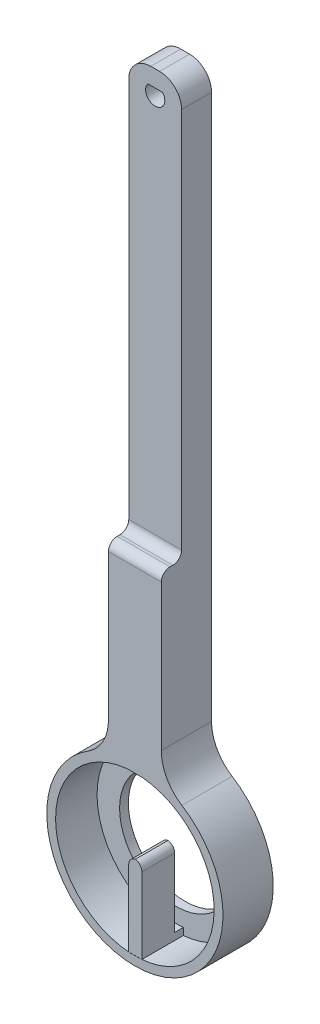
SolidWorks part; units mm, degrees
ref_plane "Front Plane" through (0, 0, 0) normal (0, 0, 1) x (1, 0, 0)
ref_plane "Top Plane" through (0, 0, 0) normal (0, 1, 0) x (1, 0, 0)
ref_plane "Right Plane" through (0, 0, 0) normal (1, 0, 0) x (0, 0, -1)
sketch "Sketch1" plane through (0, 0, 0) normal (0, 0, 1) x (1, 0, 0)
  line L1 (-4, -87.5) -> (4, -87.5)
  line L2 (-4, -87.5) -> (-4, 87.5)
  line L3 (-4, 87.5) -> (4, 87.5)
  line L4 (4, -87.5) -> (4, 87.5)
  line L5 (-4, -87.5) -> (4, 87.5) construction
  line L6 (-4, 87.5) -> (4, -87.5) construction
  circle A0 centre (0, 87.5) radius 4
  circle A1 centre (0, -87.5) radius 20
  point P0 (0, 0)
  dimension "D1" = 8
  dimension "D2" = 175
extrude "Boss-Extrude1" add sketch "Sketch1" along normal blind 13 contours A1 L4 A0 L2 | L2 A1 L4 L1 | L3 A0 | L3 A0 region at (0, -88.9381, 0) region at (0, 8.3647, 0) region at (0, 89.1977, 0) region at (0, 85.8023, 0)
extrude "Boss-Extrude2" add sketch "Sketch1<3>" along normal blind 13 contours L4 A1 L2 L1 region at (0, -77.5667, 0)
sketch "Sketch1<3>" plane through (0, 0, 0) normal (0, 0, 1) x (1, 0, 0) same geometry as "Sketch1"
sketch "Sketch2" plane through (0, 0, 13) normal (0, 0, 1) x (1, 0, 0)
  line L0 (-4, 87.5) -> (4, 87.5) construction
  line L1 (0, 84.375) -> (0, 89.875) construction
  line L2 (-1.8367, 90.0283) -> (1.8367, 90.0283)
  circle A0 centre (0, 87.5) radius 3.125
  circle A1 centre (0, 62.5) radius 3.125
  point P12 (0, 89.875)
  point P13 (0, 90.0283)
  dimension "D1" = 5.5
  dimension "D2" = 2
extrude "Cut-Extrude1" cut sketch "Sketch2" against normal blind 13 contours A0 region at (0, 87.3585, 13)
sketch "Sketch3" plane through (4, 0, 0) normal (1, 0, 0) x (0, 0, -1)
  line L1 (-13, 91.5) -> (-6.3732, 91.5)
  line L2 (-13, 91.5) -> (-13, 72.0797)
  line L3 (-13, 72.0797) -> (-6.3732, 72.0797)
  line L4 (-6.3732, 91.5) -> (-6.3732, 72.0797)
extrude "Cut-Extrude2" cut sketch "Sketch3" against normal blind 13
fillet "Fillet1" radius 10 1 edges at (0, 72.0797, 6.3732)
sketch "Sketch4" plane through (0, 0, 13) normal (0, 0, 1) x (1, 0, 0)
  line L0 (-20, -87.5) -> (20, -87.5) construction
  line L1 (0, -107.5) -> (0, -69.6414) construction
  arc A0 (-4, -67.9041) -> (4, -67.9041) centre (0, -87.5) ccw construction
  circle A1 centre (0, -87.5) radius 20
extrude "Boss-Extrude3" add sketch "Sketch4" along normal blind 13
sketch "Sketch5" plane through (4, 0, 0) normal (1, 0, 0) x (0, 0, -1)
  line L0 (-13, -67.9041) -> (-13, 72.0797) construction
  line L1 (-13, 61.0572) -> (-13, 87.5)
  line L2 (-13, 87.5) -> (-6.3732, 87.5)
  arc A0 (-6.3732, 87.5) -> (-13, 61.0572) centre (-49.1244, 84.1621) cw
extrude "Cut-Extrude3" cut sketch "Sketch5" against normal blind 13
sketch "Sketch6" plane through (0, 0, 26) normal (0, 0, 1) x (1, 0, 0)
  circle A0 centre (0, -87.5) radius 18
extrude "Cut-Extrude4" cut sketch "Sketch6" against normal blind 24
sketch "Sketch8" plane through (0, 0, 2) normal (0, 0, 1) x (1, 0, 0)
  line L0 (-1.3907, -105.4462) -> (-1.3907, -86.4462)
  line L1 (1.6093, -86.4462) -> (1.6093, -105.4279)
  line L2 (-1.3907, -86.4462) -> (1.6093, -86.4462)
  line L3 (-1.3907, -105.4462) -> (1.6093, -105.4279)
  line L4 (17.1093, -101.2315) -> (17.1093, -73.7685)
  line L5 (-16.8907, -100.8575) -> (-16.8907, -74.1425)
  circle A0 centre (0, -87.5) radius 18 construction
  point P9 (17.1093, -87.5)
  point P12 (-16.8907, -87.5)
  dimension "D1" = 3
  dimension "D2" = 19
  dimension "D3" = 15.5
  dimension "D4" = 15.5
extrude "Boss-Extrude7" add sketch "Sketch8" along normal blind 22 separate body contours L3 L1 L2 L0
fillet "Fillet5" radius 1.75 2 edges at (1.6093, -86.4462, 13) (-1.3907, -86.4462, 13)
fillet "Fillet6" radius 20 1 edges at (0, 61.0572, 13)
sketch "Sketch13" plane through (-4, 0, 0) normal (-1, 0, 0) x (0, 0, 1)
  line L0 (6.3732, 87.5) -> (6.3732, 3.1735)
  line L1 (6.3732, 3.1735) -> (13, 3.1735)
  line L2 (13, -67.9041) -> (13, 55.8052) construction
  line L3 (13, 3.1735) -> (13, 87.5)
  line L4 (13, 87.5) -> (6.3732, 87.5)
extrude "Cut-Extrude8" cut sketch "Sketch13" against normal blind 22
fillet "Fillet8" radius 21.5 1 edges at (0, 3.1735, 6.3732)
fillet "Fillet9" radius 21.5 1 edges at (0, 3.1735, 13)
sketch "Sketch14" plane through (-4, 0, 0) normal (-1, 0, 0) x (0, 0, 1)
  line L1 (6.3732, -28.0179) -> (23.434, -28.0179)
  line L2 (6.3732, -28.0179) -> (6.3732, 18.6989)
  line L3 (6.3732, 18.6989) -> (23.434, 18.6989)
  line L4 (23.434, -28.0179) -> (23.434, 18.6989)
extrude "Cut-Extrude10" cut sketch "Sketch14" against normal blind 22
sketch "Sketch23" plane through (0, 0, 0) normal (0, 0, -1) x (-1, 0, 0)
  circle A0 centre (0, -87.5) radius 16.3958
extrude "Cut-Extrude14" cut sketch "Sketch23" against normal blind 4
sketch "Sketch24" plane through (0, 0, 0) normal (0, 0, -1) x (-1, 0, 0)
  arc A0 (0, -71.1042) -> (0, -103.8958) centre (0, -87.5) ccw
  circle A1 centre (0, -87.5) radius 16.3958 construction
  arc A2 (0, -71.1042) -> (0, -103.8958) centre (0, -87.5) cw
  arc A3 (0, -74.7441) -> (0, -100.5129) centre (0, -87.6285) cw
  arc A4 (0, -74.7441) -> (0, -100.5129) centre (0, -87.6285) ccw
extrude "Boss-Extrude16" add sketch "Sketch24" against normal blind 2
sketch "Sketch25" plane through (0, 0, 26) normal (0, 0, 1) x (1, 0, 0)
  circle A0 centre (0, -87.6285) radius 20.1285
extrude "Cut-Extrude15" cut sketch "Sketch25" against normal blind 9
sketch "Sketch26" plane through (0, 0, 6.3732) normal (0, 0, 1) x (1, 0, 0)
  line L0 (-4, 80.8242) -> (-4, -28.0179) construction
  line L1 (-4, 66.3734) -> (4.8485, 66.3734)
  line L2 (-4, 66.3734) -> (-4, 92.3734)
  line L3 (-4, 92.3734) -> (4.8485, 92.3734)
  line L4 (4.8485, 66.3734) -> (4.8485, 92.3734)
  dimension "D1" = 26
extrude "Cut-Extrude16" cut sketch "Sketch26" against normal blind 9 contours L2 L1 L4 L3
sketch "Sketch27" plane through (0, 0, 6.3732) normal (0, 0, 1) x (1, 0, 0)
  line L0 (0, 58.1905) -> (0, 63.6905) construction
  line L1 (-2.1323, 63.8405) -> (2.1323, 63.8405)
  circle A0 centre (0, 61.4179) radius 3.2274
  dimension "D1" = 5.5
  dimension "D2" = 0.15
extrude "Cut-Extrude17" cut sketch "Sketch27" against normal blind 9 contours L1 A0 region at (0, 61.2051, 6.3732)
fillet "Fillet21" radius 3.5 2 edges at (4, 66.3734, 3.1866) (-4, 66.3734, 3.1866)
sketch "Sketch28" plane through (0, 0, 0) normal (0, 0, -1) x (-1, 0, 0)
  line L3 (-6, -69.5886) -> (6, -69.5886)
  line L4 (-6, -69.5886) -> (-6, -27.0166)
  line L5 (-6, -27.0166) -> (6, -27.0166)
  line L6 (6, -69.5886) -> (6, -27.0166)
  arc A0 (-2.1323, 63.8405) -> (2.1323, 63.8405) centre (0, 61.4179) ccw construction
  dimension "D1" = 12
  dimension "D2" = 6
extrude "Boss-Extrude20" add sketch "Sketch28" against normal blind 15.8
sketch "Sketch30" plane through (0, 0, 0) normal (0, 0, -1) x (-1, 0, 0)
  line L0 (2.1323, 63.8405) -> (-2.1323, 63.8405) construction
  line L1 (2.1323, 63.8405) -> (-2.1323, 63.8405)
  line L3 (-6, -27.0166) -> (6, -27.0166)
  line L4 (-6, -27.0166) -> (-6, 66.5832)
  line L5 (-6, 66.5832) -> (6, 66.5832)
  line L6 (6, -27.0166) -> (6, 66.5832)
  arc A0 (-2.1323, 63.8405) -> (2.1323, 63.8405) centre (0, 61.4179) ccw construction
  arc A1 (-2.1323, 63.8405) -> (2.1323, 63.8405) centre (0, 61.4179) ccw
  dimension "D1" = 12
extrude "Boss-Extrude21" add sketch "Sketch30" against normal blind 6.8
fillet "Fillet23" radius 5 2 edges at (6, 66.5832, 3.4) (-6, 66.5832, 3.4)
sketch "Sketch33" plane through (0, 0, 6.8) normal (0, 0, 1) x (1, 0, 0)
  line L0 (-2.0993, 63.803) -> (2.0993, 63.803)
  line L1 (-2.1323, 63.8405) -> (2.1323, 63.8405) construction
  line L2 (-2.1323, 63.8405) -> (2.1323, 63.8405)
  arc A0 (-2.1323, 63.8405) -> (2.1323, 63.8405) centre (0, 61.4179) ccw construction
  arc A1 (-2.1323, 63.8405) -> (2.1323, 63.8405) centre (0, 61.4179) ccw
  arc A2 (-2.0993, 63.803) -> (2.0993, 63.803) centre (0, 61.4179) ccw
extrude "Boss-Extrude22" add sketch "Sketch33" against normal blind 6.8
sketch "Sketch34" plane through (-6, 0, 0) normal (-1, 0, 0) x (0, 0, 1)
  line L0 (0, -107.5) -> (17, -107.5) construction
  line L1 (11.4141, -27.0166) -> (17, -27.0166)
  line L2 (11.4141, -27.0166) -> (11.4141, -107.5)
  line L3 (11.4141, -107.5) -> (17, -107.5)
  line L4 (17, -27.0166) -> (17, -107.5)
extrude "Cut-Extrude18" cut sketch "Sketch34" against normal blind 41 and the other way blind 29
fillet "Fillet27" radius 2 2 edges at (0, -27.0166, 6.8) (0, -27.0166, 11.4141)
fillet "Fillet28" radius 10 2 edges at (-6, -68.4212, 5.707) (6, -68.4212, 5.707)
sketch "Sketch35" plane through (0, 0, 6.8) normal (0, 0, 1) x (1, 0, 0)
  line L2 (2.0993, 63.803) -> (-2.0993, 63.803) construction
  line L3 (1.68, 62.803) -> (-1.68, 62.803)
  line L4 (1.68, 62.803) -> (-1.68, 62.803)
  line L5 (2.0993, 63.803) -> (-2.0993, 63.803)
  arc A1 (-2.0993, 63.803) -> (2.0993, 63.803) centre (0, 61.4179) ccw construction
  arc A2 (-1.68, 62.803) -> (1.68, 62.803) centre (0, 61.4179) ccw
  arc A3 (-1.68, 62.803) -> (1.68, 62.803) centre (0, 61.4179) ccw
  arc A4 (-2.0993, 63.803) -> (2.0993, 63.803) centre (0, 61.4179) ccw
  dimension "D1" = 1
extrude "Boss-Extrude24" add sketch "Sketch35" against normal blind 6.8
